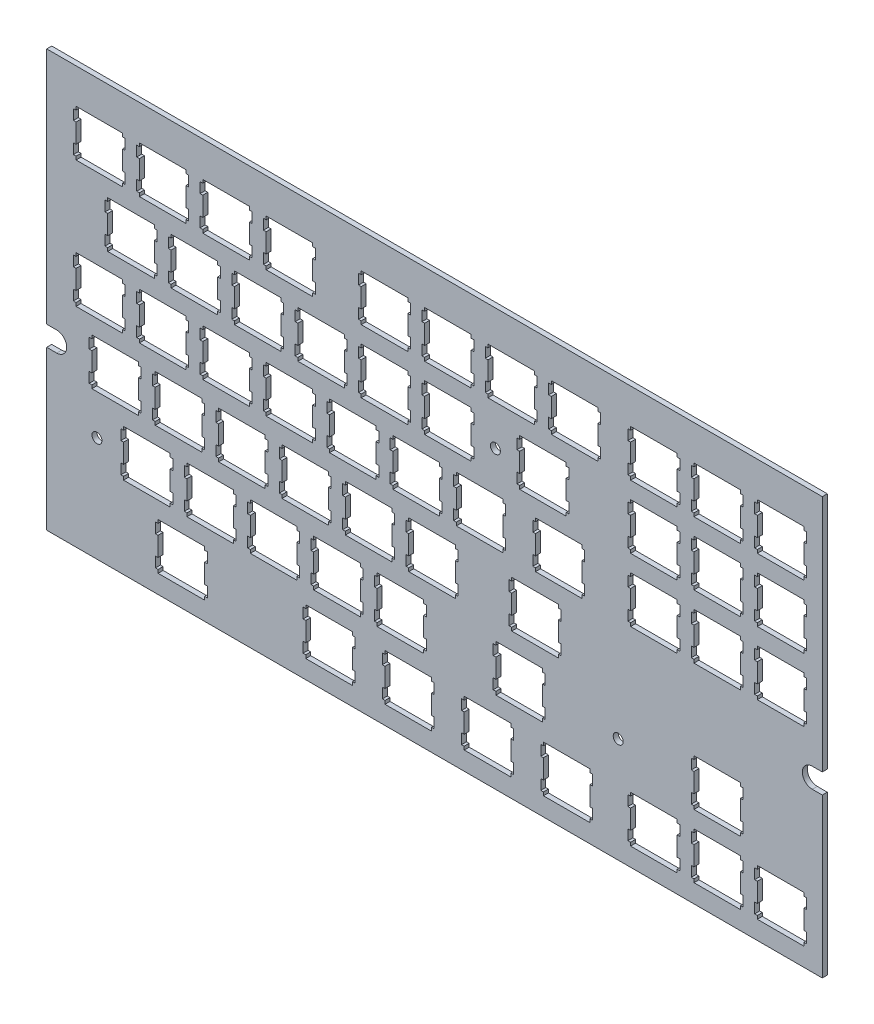
SolidWorks part; units mm, degrees
ref_plane "前视基准面" through (0, 0, 0) normal (0, 0, 1) x (1, 0, 0)
ref_plane "上视基准面" through (0, 0, 0) normal (0, 1, 0) x (1, 0, 0)
ref_plane "右视基准面" through (0, 0, 0) normal (1, 0, 0) x (0, 0, -1)
sketch "Model" plane through (0, 0, 0) normal (0, 0, 1) x (1, 0, 0)
  line L0 (613.9736, 77.7964) -> (613.9736, 76.796)
  line L1 (613.9736, 76.796) -> (613.1726, 76.796)
  line L2 (613.1726, 76.796) -> (613.1726, 73.6967)
  line L3 (613.1726, 73.6967) -> (613.9736, 73.6967)
  line L4 (613.9736, 73.6967) -> (613.9736, 67.8952)
  line L5 (613.9736, 67.8952) -> (613.1726, 67.8952)
  line L6 (613.1726, 67.8952) -> (613.1726, 64.796)
  line L7 (613.1726, 64.796) -> (613.9736, 64.796)
  line L8 (613.9736, 64.796) -> (613.9736, 63.7955)
  line L9 (613.9736, 63.7955) -> (627.9736, 63.7955)
  line L10 (627.9736, 63.7955) -> (627.9736, 64.796)
  line L11 (627.9736, 64.796) -> (628.7726, 64.796)
  line L12 (628.7726, 64.796) -> (628.7726, 67.8952)
  line L13 (628.7726, 67.8952) -> (627.9736, 67.8952)
  line L14 (627.9736, 67.8952) -> (627.9736, 73.6967)
  line L15 (627.9736, 73.6967) -> (628.7726, 73.6967)
  line L16 (628.7726, 73.6967) -> (628.7726, 76.796)
  line L17 (628.7726, 76.796) -> (627.9736, 76.796)
  line L18 (627.9736, 76.796) -> (627.9736, 77.7964)
  line L19 (627.9736, 77.7964) -> (613.9736, 77.7964)
  line L20 (594.9236, 77.7964) -> (594.9236, 76.796)
  line L21 (594.9236, 76.796) -> (594.1226, 76.796)
  line L22 (594.1226, 76.796) -> (594.1226, 73.6967)
  line L23 (594.1226, 73.6967) -> (594.9236, 73.6967)
  line L24 (594.9236, 73.6967) -> (594.9236, 67.8952)
  line L25 (594.9236, 67.8952) -> (594.1226, 67.8952)
  line L26 (594.1226, 67.8952) -> (594.1226, 64.796)
  line L27 (594.1226, 64.796) -> (594.9236, 64.796)
  line L28 (594.9236, 64.796) -> (594.9236, 63.7955)
  line L29 (594.9236, 63.7955) -> (608.9236, 63.7955)
  line L30 (608.9236, 63.7955) -> (608.9236, 64.796)
  line L31 (608.9236, 64.796) -> (609.7226, 64.796)
  line L32 (609.7226, 64.796) -> (609.7226, 67.8952)
  line L33 (609.7226, 67.8952) -> (608.9236, 67.8952)
  line L34 (608.9236, 67.8952) -> (608.9236, 73.6967)
  line L35 (608.9236, 73.6967) -> (609.7226, 73.6967)
  line L36 (609.7226, 73.6967) -> (609.7226, 76.796)
  line L37 (609.7226, 76.796) -> (608.9236, 76.796)
  line L38 (608.9236, 76.796) -> (608.9236, 77.7964)
  line L39 (608.9236, 77.7964) -> (594.9236, 77.7964)
  line L40 (575.8736, 77.7964) -> (575.8736, 76.796)
  line L41 (575.8736, 76.796) -> (575.0726, 76.796)
  line L42 (575.0726, 76.796) -> (575.0726, 73.6967)
  line L43 (575.0726, 73.6967) -> (575.8736, 73.6967)
  line L44 (575.8736, 73.6967) -> (575.8736, 67.8952)
  line L45 (575.8736, 67.8952) -> (575.0726, 67.8952)
  line L46 (575.0726, 67.8952) -> (575.0726, 64.796)
  line L47 (575.0726, 64.796) -> (575.8736, 64.796)
  line L48 (575.8736, 64.796) -> (575.8736, 63.7955)
  line L49 (575.8736, 63.7955) -> (589.8736, 63.7955)
  line L50 (589.8736, 63.7955) -> (589.8736, 64.796)
  line L51 (589.8736, 64.796) -> (590.6726, 64.796)
  line L52 (590.6726, 64.796) -> (590.6726, 67.8952)
  line L53 (590.6726, 67.8952) -> (589.8736, 67.8952)
  line L54 (589.8736, 67.8952) -> (589.8736, 73.6967)
  line L55 (589.8736, 73.6967) -> (590.6726, 73.6967)
  line L56 (590.6726, 73.6967) -> (590.6726, 76.796)
  line L57 (590.6726, 76.796) -> (589.8736, 76.796)
  line L58 (589.8736, 76.796) -> (589.8736, 77.7964)
  line L59 (589.8736, 77.7964) -> (575.8736, 77.7964)
  line L60 (549.6786, 77.7964) -> (549.6786, 76.796)
  line L61 (549.6786, 76.796) -> (548.8796, 76.796)
  line L62 (548.8796, 76.796) -> (548.8796, 73.6967)
  line L63 (548.8796, 73.6967) -> (549.6786, 73.6967)
  line L64 (549.6786, 73.6967) -> (549.6786, 67.8952)
  line L65 (549.6786, 67.8952) -> (548.8796, 67.8952)
  line L66 (548.8796, 67.8952) -> (548.8796, 64.796)
  line L67 (548.8796, 64.796) -> (549.6786, 64.796)
  line L68 (549.6786, 64.796) -> (549.6786, 63.7955)
  line L69 (549.6786, 63.7955) -> (563.6796, 63.7955)
  line L70 (563.6796, 63.7955) -> (563.6796, 64.796)
  line L71 (563.6796, 64.796) -> (564.4786, 64.796)
  line L72 (564.4786, 64.796) -> (564.4786, 67.8952)
  line L73 (564.4786, 67.8952) -> (563.6796, 67.8952)
  line L74 (563.6796, 67.8952) -> (563.6796, 73.6967)
  line L75 (563.6796, 73.6967) -> (564.4786, 73.6967)
  line L76 (564.4786, 73.6967) -> (564.4786, 76.796)
  line L77 (564.4786, 76.796) -> (563.6796, 76.796)
  line L78 (563.6796, 76.796) -> (563.6796, 77.7964)
  line L79 (563.6796, 77.7964) -> (549.6786, 77.7964)
  line L80 (525.8676, 77.7964) -> (525.8676, 76.796)
  line L81 (525.8676, 76.796) -> (525.0666, 76.796)
  line L82 (525.0666, 76.796) -> (525.0666, 73.6967)
  line L83 (525.0666, 73.6967) -> (525.8676, 73.6967)
  line L84 (525.8676, 73.6967) -> (525.8676, 67.8952)
  line L85 (525.8676, 67.8952) -> (525.0666, 67.8952)
  line L86 (525.0666, 67.8952) -> (525.0666, 64.796)
  line L87 (525.0666, 64.796) -> (525.8676, 64.796)
  line L88 (525.8676, 64.796) -> (525.8676, 63.7955)
  line L89 (525.8676, 63.7955) -> (539.8666, 63.7955)
  line L90 (539.8666, 63.7955) -> (539.8666, 64.796)
  line L91 (539.8666, 64.796) -> (540.6676, 64.796)
  line L92 (540.6676, 64.796) -> (540.6676, 67.8952)
  line L93 (540.6676, 67.8952) -> (539.8666, 67.8952)
  line L94 (539.8666, 67.8952) -> (539.8666, 73.6967)
  line L95 (539.8666, 73.6967) -> (540.6676, 73.6967)
  line L96 (540.6676, 73.6967) -> (540.6676, 76.796)
  line L97 (540.6676, 76.796) -> (539.8666, 76.796)
  line L98 (539.8666, 76.796) -> (539.8666, 77.7964)
  line L99 (539.8666, 77.7964) -> (525.8676, 77.7964)
  line L100 (502.0536, 77.7964) -> (502.0536, 76.796)
  line L101 (502.0536, 76.796) -> (501.2546, 76.796)
  line L102 (501.2546, 76.796) -> (501.2546, 73.6967)
  line L103 (501.2546, 73.6967) -> (502.0536, 73.6967)
  line L104 (502.0536, 73.6967) -> (502.0536, 67.8952)
  line L105 (502.0536, 67.8952) -> (501.2546, 67.8952)
  line L106 (501.2546, 67.8952) -> (501.2546, 64.796)
  line L107 (501.2546, 64.796) -> (502.0536, 64.796)
  line L108 (502.0536, 64.796) -> (502.0536, 63.7955)
  line L109 (502.0536, 63.7955) -> (516.0546, 63.7955)
  line L110 (516.0546, 63.7955) -> (516.0546, 64.796)
  line L111 (516.0546, 64.796) -> (516.8536, 64.796)
  line L112 (516.8536, 64.796) -> (516.8536, 67.8952)
  line L113 (516.8536, 67.8952) -> (516.0546, 67.8952)
  line L114 (516.0546, 67.8952) -> (516.0546, 73.6967)
  line L115 (516.0546, 73.6967) -> (516.8536, 73.6967)
  line L116 (516.8536, 73.6967) -> (516.8536, 76.796)
  line L117 (516.8536, 76.796) -> (516.0546, 76.796)
  line L118 (516.0546, 76.796) -> (516.0546, 77.7964)
  line L119 (516.0546, 77.7964) -> (502.0536, 77.7964)
  line L120 (478.2426, 77.7964) -> (478.2426, 76.796)
  line L121 (478.2426, 76.796) -> (477.4416, 76.796)
  line L122 (477.4416, 76.796) -> (477.4416, 73.6967)
  line L123 (477.4416, 73.6967) -> (478.2426, 73.6967)
  line L124 (478.2426, 73.6967) -> (478.2426, 67.8952)
  line L125 (478.2426, 67.8952) -> (477.4416, 67.8952)
  line L126 (477.4416, 67.8952) -> (477.4416, 64.796)
  line L127 (477.4416, 64.796) -> (478.2426, 64.796)
  line L128 (478.2426, 64.796) -> (478.2426, 63.7955)
  line L129 (478.2426, 63.7955) -> (492.2416, 63.7955)
  line L130 (492.2416, 63.7955) -> (492.2416, 64.796)
  line L131 (492.2416, 64.796) -> (493.0426, 64.796)
  line L132 (493.0426, 64.796) -> (493.0426, 67.8952)
  line L133 (493.0426, 67.8952) -> (492.2416, 67.8952)
  line L134 (492.2416, 67.8952) -> (492.2416, 73.6967)
  line L135 (492.2416, 73.6967) -> (493.0426, 73.6967)
  line L136 (493.0426, 73.6967) -> (493.0426, 76.796)
  line L137 (493.0426, 76.796) -> (492.2416, 76.796)
  line L138 (492.2416, 76.796) -> (492.2416, 77.7964)
  line L139 (492.2416, 77.7964) -> (478.2426, 77.7964)
  line L140 (594.9236, 96.8449) -> (594.9236, 95.8446)
  line L141 (594.9236, 95.8446) -> (594.1226, 95.8446)
  line L142 (594.1226, 95.8446) -> (594.1226, 92.7467)
  line L143 (594.1226, 92.7467) -> (594.9236, 92.7467)
  line L144 (594.9236, 92.7467) -> (594.9236, 86.9452)
  line L145 (594.9236, 86.9452) -> (594.1226, 86.9452)
  line L146 (594.1226, 86.9452) -> (594.1226, 83.8446)
  line L147 (594.1226, 83.8446) -> (594.9236, 83.8446)
  line L148 (594.9236, 83.8446) -> (594.9236, 82.8455)
  line L149 (594.9236, 82.8455) -> (608.9236, 82.8455)
  line L150 (608.9236, 82.8455) -> (608.9236, 83.8446)
  line L151 (608.9236, 83.8446) -> (609.7226, 83.8446)
  line L152 (609.7226, 83.8446) -> (609.7226, 86.9452)
  line L153 (609.7226, 86.9452) -> (608.9236, 86.9452)
  line L154 (608.9236, 86.9452) -> (608.9236, 92.7467)
  line L155 (608.9236, 92.7467) -> (609.7226, 92.7467)
  line L156 (609.7226, 92.7467) -> (609.7226, 95.8446)
  line L157 (609.7226, 95.8446) -> (608.9236, 95.8446)
  line L158 (608.9236, 95.8446) -> (608.9236, 96.8449)
  line L159 (608.9236, 96.8449) -> (594.9236, 96.8449)
  line L160 (499.6736, 96.8449) -> (499.6736, 95.8446)
  line L161 (499.6736, 95.8446) -> (498.8726, 95.8446)
  line L162 (498.8726, 95.8446) -> (498.8726, 92.7467)
  line L163 (498.8726, 92.7467) -> (499.6736, 92.7467)
  line L164 (499.6736, 92.7467) -> (499.6736, 86.9452)
  line L165 (499.6736, 86.9452) -> (498.8726, 86.9452)
  line L166 (498.8726, 86.9452) -> (498.8726, 83.8446)
  line L167 (498.8726, 83.8446) -> (499.6736, 83.8446)
  line L168 (499.6736, 83.8446) -> (499.6736, 82.8455)
  line L169 (499.6736, 82.8455) -> (513.6736, 82.8455)
  line L170 (513.6736, 82.8455) -> (513.6736, 83.8446)
  line L171 (513.6736, 83.8446) -> (514.4726, 83.8446)
  line L172 (514.4726, 83.8446) -> (514.4726, 86.9452)
  line L173 (514.4726, 86.9452) -> (513.6736, 86.9452)
  line L174 (513.6736, 86.9452) -> (513.6736, 92.7467)
  line L175 (513.6736, 92.7467) -> (514.4726, 92.7467)
  line L176 (514.4726, 92.7467) -> (514.4726, 95.8446)
  line L177 (514.4726, 95.8446) -> (513.6736, 95.8446)
  line L178 (513.6736, 95.8446) -> (513.6736, 96.8449)
  line L179 (513.6736, 96.8449) -> (499.6736, 96.8449)
  line L180 (480.6236, 96.8449) -> (480.6236, 95.8446)
  line L181 (480.6236, 95.8446) -> (479.8226, 95.8446)
  line L182 (479.8226, 95.8446) -> (479.8226, 92.7467)
  line L183 (479.8226, 92.7467) -> (480.6236, 92.7467)
  line L184 (480.6236, 92.7467) -> (480.6236, 86.9452)
  line L185 (480.6236, 86.9452) -> (479.8226, 86.9452)
  line L186 (479.8226, 86.9452) -> (479.8226, 83.8446)
  line L187 (479.8226, 83.8446) -> (480.6236, 83.8446)
  line L188 (480.6236, 83.8446) -> (480.6236, 82.8455)
  line L189 (480.6236, 82.8455) -> (494.6236, 82.8455)
  line L190 (494.6236, 82.8455) -> (494.6236, 83.8446)
  line L191 (494.6236, 83.8446) -> (495.4226, 83.8446)
  line L192 (495.4226, 83.8446) -> (495.4226, 86.9452)
  line L193 (495.4226, 86.9452) -> (494.6236, 86.9452)
  line L194 (494.6236, 86.9452) -> (494.6236, 92.7467)
  line L195 (494.6236, 92.7467) -> (495.4226, 92.7467)
  line L196 (495.4226, 92.7467) -> (495.4226, 95.8446)
  line L197 (495.4226, 95.8446) -> (494.6236, 95.8446)
  line L198 (494.6236, 95.8446) -> (494.6236, 96.8449)
  line L199 (494.6236, 96.8449) -> (480.6236, 96.8449)
  line L200 (461.5736, 96.8449) -> (461.5736, 95.8446)
  line L201 (461.5736, 95.8446) -> (460.7726, 95.8446)
  line L202 (460.7726, 95.8446) -> (460.7726, 92.7467)
  line L203 (460.7726, 92.7467) -> (461.5736, 92.7467)
  line L204 (461.5736, 92.7467) -> (461.5736, 86.9452)
  line L205 (461.5736, 86.9452) -> (460.7726, 86.9452)
  line L206 (460.7726, 86.9452) -> (460.7726, 83.8446)
  line L207 (460.7726, 83.8446) -> (461.5736, 83.8446)
  line L208 (461.5736, 83.8446) -> (461.5736, 82.8455)
  line L209 (461.5736, 82.8455) -> (475.5736, 82.8455)
  line L210 (475.5736, 82.8455) -> (475.5736, 83.8446)
  line L211 (475.5736, 83.8446) -> (476.3726, 83.8446)
  line L212 (476.3726, 83.8446) -> (476.3726, 86.9452)
  line L213 (476.3726, 86.9452) -> (475.5736, 86.9452)
  line L214 (475.5736, 86.9452) -> (475.5736, 92.7467)
  line L215 (475.5736, 92.7467) -> (476.3726, 92.7467)
  line L216 (476.3726, 92.7467) -> (476.3726, 95.8446)
  line L217 (476.3726, 95.8446) -> (475.5736, 95.8446)
  line L218 (475.5736, 95.8446) -> (475.5736, 96.8449)
  line L219 (475.5736, 96.8449) -> (461.5736, 96.8449)
  line L220 (442.5236, 96.8449) -> (442.5236, 95.8446)
  line L221 (442.5236, 95.8446) -> (441.7226, 95.8446)
  line L222 (441.7226, 95.8446) -> (441.7226, 92.7467)
  line L223 (441.7226, 92.7467) -> (442.5236, 92.7467)
  line L224 (442.5236, 92.7467) -> (442.5236, 86.9452)
  line L225 (442.5236, 86.9452) -> (441.7226, 86.9452)
  line L226 (441.7226, 86.9452) -> (441.7226, 83.8446)
  line L227 (441.7226, 83.8446) -> (442.5236, 83.8446)
  line L228 (442.5236, 83.8446) -> (442.5236, 82.8455)
  line L229 (442.5236, 82.8455) -> (456.5236, 82.8455)
  line L230 (456.5236, 82.8455) -> (456.5236, 83.8446)
  line L231 (456.5236, 83.8446) -> (457.3226, 83.8446)
  line L232 (457.3226, 83.8446) -> (457.3226, 86.9452)
  line L233 (457.3226, 86.9452) -> (456.5236, 86.9452)
  line L234 (456.5236, 86.9452) -> (456.5236, 92.7467)
  line L235 (456.5236, 92.7467) -> (457.3226, 92.7467)
  line L236 (457.3226, 92.7467) -> (457.3226, 95.8446)
  line L237 (457.3226, 95.8446) -> (456.5236, 95.8446)
  line L238 (456.5236, 95.8446) -> (456.5236, 96.8449)
  line L239 (456.5236, 96.8449) -> (442.5236, 96.8449)
  line L240 (423.4736, 96.8449) -> (423.4736, 95.8446)
  line L241 (423.4736, 95.8446) -> (422.6726, 95.8446)
  line L242 (422.6726, 95.8446) -> (422.6726, 92.7467)
  line L243 (422.6726, 92.7467) -> (423.4736, 92.7467)
  line L244 (423.4736, 92.7467) -> (423.4736, 86.9452)
  line L245 (423.4736, 86.9452) -> (422.6726, 86.9452)
  line L246 (422.6726, 86.9452) -> (422.6726, 83.8446)
  line L247 (422.6726, 83.8446) -> (423.4736, 83.8446)
  line L248 (423.4736, 83.8446) -> (423.4736, 82.8455)
  line L249 (423.4736, 82.8455) -> (437.4736, 82.8455)
  line L250 (437.4736, 82.8455) -> (437.4736, 83.8446)
  line L251 (437.4736, 83.8446) -> (438.2726, 83.8446)
  line L252 (438.2726, 83.8446) -> (438.2726, 86.9452)
  line L253 (438.2726, 86.9452) -> (437.4736, 86.9452)
  line L254 (437.4736, 86.9452) -> (437.4736, 92.7467)
  line L255 (437.4736, 92.7467) -> (438.2726, 92.7467)
  line L256 (438.2726, 92.7467) -> (438.2726, 95.8446)
  line L257 (438.2726, 95.8446) -> (437.4736, 95.8446)
  line L258 (437.4736, 95.8446) -> (437.4736, 96.8449)
  line L259 (437.4736, 96.8449) -> (423.4736, 96.8449)
  line L260 (540.1536, 115.895) -> (540.1536, 114.8945)
  line L261 (540.1536, 114.8945) -> (539.3526, 114.8945)
  line L262 (539.3526, 114.8945) -> (539.3526, 111.7967)
  line L263 (539.3526, 111.7967) -> (540.1536, 111.7967)
  line L264 (540.1536, 111.7967) -> (540.1536, 105.9953)
  line L265 (540.1536, 105.9953) -> (539.3526, 105.9953)
  line L266 (539.3526, 105.9953) -> (539.3526, 102.8947)
  line L267 (539.3526, 102.8947) -> (540.1536, 102.8947)
  line L268 (540.1536, 102.8947) -> (540.1536, 101.8957)
  line L269 (540.1536, 101.8957) -> (554.1546, 101.8957)
  line L270 (554.1546, 101.8957) -> (554.1546, 102.8947)
  line L271 (554.1546, 102.8947) -> (554.9536, 102.8947)
  line L272 (554.9536, 102.8947) -> (554.9536, 105.9953)
  line L273 (554.9536, 105.9953) -> (554.1546, 105.9953)
  line L274 (554.1546, 105.9953) -> (554.1546, 111.7967)
  line L275 (554.1546, 111.7967) -> (554.9536, 111.7967)
  line L276 (554.9536, 111.7967) -> (554.9536, 114.8945)
  line L277 (554.9536, 114.8945) -> (554.1546, 114.8945)
  line L278 (554.1546, 114.8945) -> (554.1546, 115.895)
  line L279 (554.1546, 115.895) -> (540.1536, 115.895)
  line L280 (509.1986, 115.895) -> (509.1986, 114.8945)
  line L281 (509.1986, 114.8945) -> (508.3976, 114.8945)
  line L282 (508.3976, 114.8945) -> (508.3976, 111.7967)
  line L283 (508.3976, 111.7967) -> (509.1986, 111.7967)
  line L284 (509.1986, 111.7967) -> (509.1986, 105.9953)
  line L285 (509.1986, 105.9953) -> (508.3976, 105.9953)
  line L286 (508.3976, 105.9953) -> (508.3976, 102.8947)
  line L287 (508.3976, 102.8947) -> (509.1986, 102.8947)
  line L288 (509.1986, 102.8947) -> (509.1986, 101.8957)
  line L289 (509.1986, 101.8957) -> (523.1986, 101.8957)
  line L290 (523.1986, 101.8957) -> (523.1986, 102.8947)
  line L291 (523.1986, 102.8947) -> (523.9976, 102.8947)
  line L292 (523.9976, 102.8947) -> (523.9976, 105.9953)
  line L293 (523.9976, 105.9953) -> (523.1986, 105.9953)
  line L294 (523.1986, 105.9953) -> (523.1986, 111.7967)
  line L295 (523.1986, 111.7967) -> (523.9976, 111.7967)
  line L296 (523.9976, 111.7967) -> (523.9976, 114.8945)
  line L297 (523.9976, 114.8945) -> (523.1986, 114.8945)
  line L298 (523.1986, 114.8945) -> (523.1986, 115.895)
  line L299 (523.1986, 115.895) -> (509.1986, 115.895)
  line L300 (490.1486, 115.895) -> (490.1486, 114.8945)
  line L301 (490.1486, 114.8945) -> (489.3476, 114.8945)
  line L302 (489.3476, 114.8945) -> (489.3476, 111.7967)
  line L303 (489.3476, 111.7967) -> (490.1486, 111.7967)
  line L304 (490.1486, 111.7967) -> (490.1486, 105.9953)
  line L305 (490.1486, 105.9953) -> (489.3476, 105.9953)
  line L306 (489.3476, 105.9953) -> (489.3476, 102.8947)
  line L307 (489.3476, 102.8947) -> (490.1486, 102.8947)
  line L308 (490.1486, 102.8947) -> (490.1486, 101.8957)
  line L309 (490.1486, 101.8957) -> (504.1486, 101.8957)
  line L310 (504.1486, 101.8957) -> (504.1486, 102.8947)
  line L311 (504.1486, 102.8947) -> (504.9476, 102.8947)
  line L312 (504.9476, 102.8947) -> (504.9476, 105.9953)
  line L313 (504.9476, 105.9953) -> (504.1486, 105.9953)
  line L314 (504.1486, 105.9953) -> (504.1486, 111.7967)
  line L315 (504.1486, 111.7967) -> (504.9476, 111.7967)
  line L316 (504.9476, 111.7967) -> (504.9476, 114.8945)
  line L317 (504.9476, 114.8945) -> (504.1486, 114.8945)
  line L318 (504.1486, 114.8945) -> (504.1486, 115.895)
  line L319 (504.1486, 115.895) -> (490.1486, 115.895)
  line L320 (471.0986, 115.895) -> (471.0986, 114.8945)
  line L321 (471.0986, 114.8945) -> (470.2976, 114.8945)
  line L322 (470.2976, 114.8945) -> (470.2976, 111.7967)
  line L323 (470.2976, 111.7967) -> (471.0986, 111.7967)
  line L324 (471.0986, 111.7967) -> (471.0986, 105.9953)
  line L325 (471.0986, 105.9953) -> (470.2976, 105.9953)
  line L326 (470.2976, 105.9953) -> (470.2976, 102.8947)
  line L327 (470.2976, 102.8947) -> (471.0986, 102.8947)
  line L328 (471.0986, 102.8947) -> (471.0986, 101.8957)
  line L329 (471.0986, 101.8957) -> (485.0986, 101.8957)
  line L330 (485.0986, 101.8957) -> (485.0986, 102.8947)
  line L331 (485.0986, 102.8947) -> (485.8976, 102.8947)
  line L332 (485.8976, 102.8947) -> (485.8976, 105.9953)
  line L333 (485.8976, 105.9953) -> (485.0986, 105.9953)
  line L334 (485.0986, 105.9953) -> (485.0986, 111.7967)
  line L335 (485.0986, 111.7967) -> (485.8976, 111.7967)
  line L336 (485.8976, 111.7967) -> (485.8976, 114.8945)
  line L337 (485.8976, 114.8945) -> (485.0986, 114.8945)
  line L338 (485.0986, 114.8945) -> (485.0986, 115.895)
  line L339 (485.0986, 115.895) -> (471.0986, 115.895)
  line L340 (452.0486, 115.895) -> (452.0486, 114.8945)
  line L341 (452.0486, 114.8945) -> (451.2476, 114.8945)
  line L342 (451.2476, 114.8945) -> (451.2476, 111.7967)
  line L343 (451.2476, 111.7967) -> (452.0486, 111.7967)
  line L344 (452.0486, 111.7967) -> (452.0486, 105.9953)
  line L345 (452.0486, 105.9953) -> (451.2476, 105.9953)
  line L346 (451.2476, 105.9953) -> (451.2476, 102.8947)
  line L347 (451.2476, 102.8947) -> (452.0486, 102.8947)
  line L348 (452.0486, 102.8947) -> (452.0486, 101.8957)
  line L349 (452.0486, 101.8957) -> (466.0486, 101.8957)
  line L350 (466.0486, 101.8957) -> (466.0486, 102.8947)
  line L351 (466.0486, 102.8947) -> (466.8476, 102.8947)
  line L352 (466.8476, 102.8947) -> (466.8476, 105.9953)
  line L353 (466.8476, 105.9953) -> (466.0486, 105.9953)
  line L354 (466.0486, 105.9953) -> (466.0486, 111.7967)
  line L355 (466.0486, 111.7967) -> (466.8476, 111.7967)
  line L356 (466.8476, 111.7967) -> (466.8476, 114.8945)
  line L357 (466.8476, 114.8945) -> (466.0486, 114.8945)
  line L358 (466.0486, 114.8945) -> (466.0486, 115.895)
  line L359 (466.0486, 115.895) -> (452.0486, 115.895)
  line L360 (432.9986, 115.895) -> (432.9986, 114.8945)
  line L361 (432.9986, 114.8945) -> (432.1976, 114.8945)
  line L362 (432.1976, 114.8945) -> (432.1976, 111.7967)
  line L363 (432.1976, 111.7967) -> (432.9986, 111.7967)
  line L364 (432.9986, 111.7967) -> (432.9986, 105.9953)
  line L365 (432.9986, 105.9953) -> (432.1976, 105.9953)
  line L366 (432.1976, 105.9953) -> (432.1976, 102.8947)
  line L367 (432.1976, 102.8947) -> (432.9986, 102.8947)
  line L368 (432.9986, 102.8947) -> (432.9986, 101.8957)
  line L369 (432.9986, 101.8957) -> (446.9986, 101.8957)
  line L370 (446.9986, 101.8957) -> (446.9986, 102.8947)
  line L371 (446.9986, 102.8947) -> (447.7976, 102.8947)
  line L372 (447.7976, 102.8947) -> (447.7976, 105.9953)
  line L373 (447.7976, 105.9953) -> (446.9986, 105.9953)
  line L374 (446.9986, 105.9953) -> (446.9986, 111.7967)
  line L375 (446.9986, 111.7967) -> (447.7976, 111.7967)
  line L376 (447.7976, 111.7967) -> (447.7976, 114.8945)
  line L377 (447.7976, 114.8945) -> (446.9986, 114.8945)
  line L378 (446.9986, 114.8945) -> (446.9986, 115.895)
  line L379 (446.9986, 115.895) -> (432.9986, 115.895)
  line L380 (413.9486, 115.895) -> (413.9486, 114.8945)
  line L381 (413.9486, 114.8945) -> (413.1476, 114.8945)
  line L382 (413.1476, 114.8945) -> (413.1476, 111.7967)
  line L383 (413.1476, 111.7967) -> (413.9486, 111.7967)
  line L384 (413.9486, 111.7967) -> (413.9486, 105.9953)
  line L385 (413.9486, 105.9953) -> (413.1476, 105.9953)
  line L386 (413.1476, 105.9953) -> (413.1476, 102.8947)
  line L387 (413.1476, 102.8947) -> (413.9486, 102.8947)
  line L388 (413.9486, 102.8947) -> (413.9486, 101.8957)
  line L389 (413.9486, 101.8957) -> (427.9486, 101.8957)
  line L390 (427.9486, 101.8957) -> (427.9486, 102.8947)
  line L391 (427.9486, 102.8947) -> (428.7476, 102.8947)
  line L392 (428.7476, 102.8947) -> (428.7476, 105.9953)
  line L393 (428.7476, 105.9953) -> (427.9486, 105.9953)
  line L394 (427.9486, 105.9953) -> (427.9486, 111.7967)
  line L395 (427.9486, 111.7967) -> (428.7476, 111.7967)
  line L396 (428.7476, 111.7967) -> (428.7476, 114.8945)
  line L397 (428.7476, 114.8945) -> (427.9486, 114.8945)
  line L398 (427.9486, 114.8945) -> (427.9486, 115.895)
  line L399 (427.9486, 115.895) -> (413.9486, 115.895)
  line L400 (613.9736, 134.945) -> (613.9736, 133.9445)
  line L401 (613.9736, 133.9445) -> (613.1726, 133.9445)
  line L402 (613.1726, 133.9445) -> (613.1726, 130.8453)
  line L403 (613.1726, 130.8453) -> (613.9736, 130.8453)
  line L404 (613.9736, 130.8453) -> (613.9736, 125.0453)
  line L405 (613.9736, 125.0453) -> (613.1726, 125.0453)
  line L406 (613.1726, 125.0453) -> (613.1726, 121.9447)
  line L407 (613.1726, 121.9447) -> (613.9736, 121.9447)
  line L408 (613.9736, 121.9447) -> (613.9736, 120.9457)
  line L409 (613.9736, 120.9457) -> (627.9736, 120.9457)
  line L410 (627.9736, 120.9457) -> (627.9736, 121.9447)
  line L411 (627.9736, 121.9447) -> (628.7726, 121.9447)
  line L412 (628.7726, 121.9447) -> (628.7726, 125.0453)
  line L413 (628.7726, 125.0453) -> (627.9736, 125.0453)
  line L414 (627.9736, 125.0453) -> (627.9736, 130.8453)
  line L415 (627.9736, 130.8453) -> (628.7726, 130.8453)
  line L416 (628.7726, 130.8453) -> (628.7726, 133.9445)
  line L417 (628.7726, 133.9445) -> (627.9736, 133.9445)
  line L418 (627.9736, 133.9445) -> (627.9736, 134.945)
  line L419 (627.9736, 134.945) -> (613.9736, 134.945)
  line L420 (594.9236, 134.945) -> (594.9236, 133.9445)
  line L421 (594.9236, 133.9445) -> (594.1226, 133.9445)
  line L422 (594.1226, 133.9445) -> (594.1226, 130.8453)
  line L423 (594.1226, 130.8453) -> (594.9236, 130.8453)
  line L424 (594.9236, 130.8453) -> (594.9236, 125.0453)
  line L425 (594.9236, 125.0453) -> (594.1226, 125.0453)
  line L426 (594.1226, 125.0453) -> (594.1226, 121.9447)
  line L427 (594.1226, 121.9447) -> (594.9236, 121.9447)
  line L428 (594.9236, 121.9447) -> (594.9236, 120.9457)
  line L429 (594.9236, 120.9457) -> (608.9236, 120.9457)
  line L430 (608.9236, 120.9457) -> (608.9236, 121.9447)
  line L431 (608.9236, 121.9447) -> (609.7226, 121.9447)
  line L432 (609.7226, 121.9447) -> (609.7226, 125.0453)
  line L433 (609.7226, 125.0453) -> (608.9236, 125.0453)
  line L434 (608.9236, 125.0453) -> (608.9236, 130.8453)
  line L435 (608.9236, 130.8453) -> (609.7226, 130.8453)
  line L436 (609.7226, 130.8453) -> (609.7226, 133.9445)
  line L437 (609.7226, 133.9445) -> (608.9236, 133.9445)
  line L438 (608.9236, 133.9445) -> (608.9236, 134.945)
  line L439 (608.9236, 134.945) -> (594.9236, 134.945)
  line L440 (575.8736, 134.945) -> (575.8736, 133.9445)
  line L441 (575.8736, 133.9445) -> (575.0726, 133.9445)
  line L442 (575.0726, 133.9445) -> (575.0726, 130.8453)
  line L443 (575.0726, 130.8453) -> (575.8736, 130.8453)
  line L444 (575.8736, 130.8453) -> (575.8736, 125.0453)
  line L445 (575.8736, 125.0453) -> (575.0726, 125.0453)
  line L446 (575.0726, 125.0453) -> (575.0726, 121.9447)
  line L447 (575.0726, 121.9447) -> (575.8736, 121.9447)
  line L448 (575.8736, 121.9447) -> (575.8736, 120.9457)
  line L449 (575.8736, 120.9457) -> (589.8736, 120.9457)
  line L450 (589.8736, 120.9457) -> (589.8736, 121.9447)
  line L451 (589.8736, 121.9447) -> (590.6726, 121.9447)
  line L452 (590.6726, 121.9447) -> (590.6726, 125.0453)
  line L453 (590.6726, 125.0453) -> (589.8736, 125.0453)
  line L454 (589.8736, 125.0453) -> (589.8736, 130.8453)
  line L455 (589.8736, 130.8453) -> (590.6726, 130.8453)
  line L456 (590.6726, 130.8453) -> (590.6726, 133.9445)
  line L457 (590.6726, 133.9445) -> (589.8736, 133.9445)
  line L458 (589.8736, 133.9445) -> (589.8736, 134.945)
  line L459 (589.8736, 134.945) -> (575.8736, 134.945)
  line L460 (547.2986, 134.945) -> (547.2986, 133.9445)
  line L461 (547.2986, 133.9445) -> (546.4976, 133.9445)
  line L462 (546.4976, 133.9445) -> (546.4976, 130.8453)
  line L463 (546.4976, 130.8453) -> (547.2986, 130.8453)
  line L464 (547.2986, 130.8453) -> (547.2986, 125.0453)
  line L465 (547.2986, 125.0453) -> (546.4976, 125.0453)
  line L466 (546.4976, 125.0453) -> (546.4976, 121.9447)
  line L467 (546.4976, 121.9447) -> (547.2986, 121.9447)
  line L468 (547.2986, 121.9447) -> (547.2986, 120.9457)
  line L469 (547.2986, 120.9457) -> (561.2986, 120.9457)
  line L470 (561.2986, 120.9457) -> (561.2986, 121.9447)
  line L471 (561.2986, 121.9447) -> (562.0976, 121.9447)
  line L472 (562.0976, 121.9447) -> (562.0976, 125.0453)
  line L473 (562.0976, 125.0453) -> (561.2986, 125.0453)
  line L474 (561.2986, 125.0453) -> (561.2986, 130.8453)
  line L475 (561.2986, 130.8453) -> (562.0976, 130.8453)
  line L476 (562.0976, 130.8453) -> (562.0976, 133.9445)
  line L477 (562.0976, 133.9445) -> (561.2986, 133.9445)
  line L478 (561.2986, 133.9445) -> (561.2986, 134.945)
  line L479 (561.2986, 134.945) -> (547.2986, 134.945)
  line L480 (523.4866, 134.945) -> (523.4866, 133.9445)
  line L481 (523.4866, 133.9445) -> (522.6856, 133.9445)
  line L482 (522.6856, 133.9445) -> (522.6856, 130.8453)
  line L483 (522.6856, 130.8453) -> (523.4866, 130.8453)
  line L484 (523.4866, 130.8453) -> (523.4866, 125.0453)
  line L485 (523.4866, 125.0453) -> (522.6856, 125.0453)
  line L486 (522.6856, 125.0453) -> (522.6856, 121.9447)
  line L487 (522.6856, 121.9447) -> (523.4866, 121.9447)
  line L488 (523.4866, 121.9447) -> (523.4866, 120.9457)
  line L489 (523.4866, 120.9457) -> (537.4856, 120.9457)
  line L490 (537.4856, 120.9457) -> (537.4856, 121.9447)
  line L491 (537.4856, 121.9447) -> (538.2866, 121.9447)
  line L492 (538.2866, 121.9447) -> (538.2866, 125.0453)
  line L493 (538.2866, 125.0453) -> (537.4856, 125.0453)
  line L494 (537.4856, 125.0453) -> (537.4856, 130.8453)
  line L495 (537.4856, 130.8453) -> (538.2866, 130.8453)
  line L496 (538.2866, 130.8453) -> (538.2866, 133.9445)
  line L497 (538.2866, 133.9445) -> (537.4856, 133.9445)
  line L498 (537.4856, 133.9445) -> (537.4856, 134.945)
  line L499 (537.4856, 134.945) -> (523.4866, 134.945)
  line L500 (504.4366, 134.945) -> (504.4366, 133.9445)
  line L501 (504.4366, 133.9445) -> (503.6356, 133.9445)
  line L502 (503.6356, 133.9445) -> (503.6356, 130.8453)
  line L503 (503.6356, 130.8453) -> (504.4366, 130.8453)
  line L504 (504.4366, 130.8453) -> (504.4366, 125.0453)
  line L505 (504.4366, 125.0453) -> (503.6356, 125.0453)
  line L506 (503.6356, 125.0453) -> (503.6356, 121.9447)
  line L507 (503.6356, 121.9447) -> (504.4366, 121.9447)
  line L508 (504.4366, 121.9447) -> (504.4366, 120.9457)
  line L509 (504.4366, 120.9457) -> (518.4356, 120.9457)
  line L510 (518.4356, 120.9457) -> (518.4356, 121.9447)
  line L511 (518.4356, 121.9447) -> (519.2366, 121.9447)
  line L512 (519.2366, 121.9447) -> (519.2366, 125.0453)
  line L513 (519.2366, 125.0453) -> (518.4356, 125.0453)
  line L514 (518.4356, 125.0453) -> (518.4356, 130.8453)
  line L515 (518.4356, 130.8453) -> (519.2366, 130.8453)
  line L516 (519.2366, 130.8453) -> (519.2366, 133.9445)
  line L517 (519.2366, 133.9445) -> (518.4356, 133.9445)
  line L518 (518.4356, 133.9445) -> (518.4356, 134.945)
  line L519 (518.4356, 134.945) -> (504.4366, 134.945)
  line L520 (485.3866, 134.945) -> (485.3866, 133.9445)
  line L521 (485.3866, 133.9445) -> (484.5856, 133.9445)
  line L522 (484.5856, 133.9445) -> (484.5856, 130.8453)
  line L523 (484.5856, 130.8453) -> (485.3866, 130.8453)
  line L524 (485.3866, 130.8453) -> (485.3866, 125.0453)
  line L525 (485.3866, 125.0453) -> (484.5856, 125.0453)
  line L526 (484.5856, 125.0453) -> (484.5856, 121.9447)
  line L527 (484.5856, 121.9447) -> (485.3866, 121.9447)
  line L528 (485.3866, 121.9447) -> (485.3866, 120.9457)
  line L529 (485.3866, 120.9457) -> (499.3856, 120.9457)
  line L530 (499.3856, 120.9457) -> (499.3856, 121.9447)
  line L531 (499.3856, 121.9447) -> (500.1866, 121.9447)
  line L532 (500.1866, 121.9447) -> (500.1866, 125.0453)
  line L533 (500.1866, 125.0453) -> (499.3856, 125.0453)
  line L534 (499.3856, 125.0453) -> (499.3856, 130.8453)
  line L535 (499.3856, 130.8453) -> (500.1866, 130.8453)
  line L536 (500.1866, 130.8453) -> (500.1866, 133.9445)
  line L537 (500.1866, 133.9445) -> (499.3856, 133.9445)
  line L538 (499.3856, 133.9445) -> (499.3856, 134.945)
  line L539 (499.3856, 134.945) -> (485.3866, 134.945)
  line L540 (466.3366, 134.945) -> (466.3366, 133.9445)
  line L541 (466.3366, 133.9445) -> (465.5356, 133.9445)
  line L542 (465.5356, 133.9445) -> (465.5356, 130.8453)
  line L543 (465.5356, 130.8453) -> (466.3366, 130.8453)
  line L544 (466.3366, 130.8453) -> (466.3366, 125.0453)
  line L545 (466.3366, 125.0453) -> (465.5356, 125.0453)
  line L546 (465.5356, 125.0453) -> (465.5356, 121.9447)
  line L547 (465.5356, 121.9447) -> (466.3366, 121.9447)
  line L548 (466.3366, 121.9447) -> (466.3366, 120.9457)
  line L549 (466.3366, 120.9457) -> (480.3356, 120.9457)
  line L550 (480.3356, 120.9457) -> (480.3356, 121.9447)
  line L551 (480.3356, 121.9447) -> (481.1366, 121.9447)
  line L552 (481.1366, 121.9447) -> (481.1366, 125.0453)
  line L553 (481.1366, 125.0453) -> (480.3356, 125.0453)
  line L554 (480.3356, 125.0453) -> (480.3356, 130.8453)
  line L555 (480.3356, 130.8453) -> (481.1366, 130.8453)
  line L556 (481.1366, 130.8453) -> (481.1366, 133.9445)
  line L557 (481.1366, 133.9445) -> (480.3356, 133.9445)
  line L558 (480.3356, 133.9445) -> (480.3356, 134.945)
  line L559 (480.3356, 134.945) -> (466.3366, 134.945)
  line L560 (447.2866, 134.945) -> (447.2866, 133.9445)
  line L561 (447.2866, 133.9445) -> (446.4856, 133.9445)
  line L562 (446.4856, 133.9445) -> (446.4856, 130.8453)
  line L563 (446.4856, 130.8453) -> (447.2866, 130.8453)
  line L564 (447.2866, 130.8453) -> (447.2866, 125.0453)
  line L565 (447.2866, 125.0453) -> (446.4856, 125.0453)
  line L566 (446.4856, 125.0453) -> (446.4856, 121.9447)
  line L567 (446.4856, 121.9447) -> (447.2866, 121.9447)
  line L568 (447.2866, 121.9447) -> (447.2866, 120.9457)
  line L569 (447.2866, 120.9457) -> (461.2856, 120.9457)
  line L570 (461.2856, 120.9457) -> (461.2856, 121.9447)
  line L571 (461.2856, 121.9447) -> (462.0866, 121.9447)
  line L572 (462.0866, 121.9447) -> (462.0866, 125.0453)
  line L573 (462.0866, 125.0453) -> (461.2856, 125.0453)
  line L574 (461.2856, 125.0453) -> (461.2856, 130.8453)
  line L575 (461.2856, 130.8453) -> (462.0866, 130.8453)
  line L576 (462.0866, 130.8453) -> (462.0866, 133.9445)
  line L577 (462.0866, 133.9445) -> (461.2856, 133.9445)
  line L578 (461.2856, 133.9445) -> (461.2856, 134.945)
  line L579 (461.2856, 134.945) -> (447.2866, 134.945)
  line L580 (428.2366, 134.945) -> (428.2366, 133.9445)
  line L581 (428.2366, 133.9445) -> (427.4356, 133.9445)
  line L582 (427.4356, 133.9445) -> (427.4356, 130.8453)
  line L583 (427.4356, 130.8453) -> (428.2366, 130.8453)
  line L584 (428.2366, 130.8453) -> (428.2366, 125.0453)
  line L585 (428.2366, 125.0453) -> (427.4356, 125.0453)
  line L586 (427.4356, 125.0453) -> (427.4356, 121.9447)
  line L587 (427.4356, 121.9447) -> (428.2366, 121.9447)
  line L588 (428.2366, 121.9447) -> (428.2366, 120.9457)
  line L589 (428.2366, 120.9457) -> (442.2356, 120.9457)
  line L590 (442.2356, 120.9457) -> (442.2356, 121.9447)
  line L591 (442.2356, 121.9447) -> (443.0366, 121.9447)
  line L592 (443.0366, 121.9447) -> (443.0366, 125.0453)
  line L593 (443.0366, 125.0453) -> (442.2356, 125.0453)
  line L594 (442.2356, 125.0453) -> (442.2356, 130.8453)
  line L595 (442.2356, 130.8453) -> (443.0366, 130.8453)
  line L596 (443.0366, 130.8453) -> (443.0366, 133.9445)
  line L597 (443.0366, 133.9445) -> (442.2356, 133.9445)
  line L598 (442.2356, 133.9445) -> (442.2356, 134.945)
  line L599 (442.2356, 134.945) -> (428.2366, 134.945)
  line L600 (409.1866, 134.945) -> (409.1866, 133.9445)
  line L601 (409.1866, 133.9445) -> (408.3856, 133.9445)
  line L602 (408.3856, 133.9445) -> (408.3856, 130.8453)
  line L603 (408.3856, 130.8453) -> (409.1866, 130.8453)
  line L604 (409.1866, 130.8453) -> (409.1866, 125.0453)
  line L605 (409.1866, 125.0453) -> (408.3856, 125.0453)
  line L606 (408.3856, 125.0453) -> (408.3856, 121.9447)
  line L607 (408.3856, 121.9447) -> (409.1866, 121.9447)
  line L608 (409.1866, 121.9447) -> (409.1866, 120.9457)
  line L609 (409.1866, 120.9457) -> (423.1856, 120.9457)
  line L610 (423.1856, 120.9457) -> (423.1856, 121.9447)
  line L611 (423.1856, 121.9447) -> (423.9866, 121.9447)
  line L612 (423.9866, 121.9447) -> (423.9866, 125.0453)
  line L613 (423.9866, 125.0453) -> (423.1856, 125.0453)
  line L614 (423.1856, 125.0453) -> (423.1856, 130.8453)
  line L615 (423.1856, 130.8453) -> (423.9866, 130.8453)
  line L616 (423.9866, 130.8453) -> (423.9866, 133.9445)
  line L617 (423.9866, 133.9445) -> (423.1856, 133.9445)
  line L618 (423.1856, 133.9445) -> (423.1856, 134.945)
  line L619 (423.1856, 134.945) -> (409.1866, 134.945)
  line L620 (613.9736, 153.995) -> (613.9736, 152.9945)
  line L621 (613.9736, 152.9945) -> (613.1726, 152.9945)
  line L622 (613.1726, 152.9945) -> (613.1726, 149.8953)
  line L623 (613.1726, 149.8953) -> (613.9736, 149.8953)
  line L624 (613.9736, 149.8953) -> (613.9736, 144.0953)
  line L625 (613.9736, 144.0953) -> (613.1726, 144.0953)
  line L626 (613.1726, 144.0953) -> (613.1726, 140.9947)
  line L627 (613.1726, 140.9947) -> (613.9736, 140.9947)
  line L628 (613.9736, 140.9947) -> (613.9736, 139.9957)
  line L629 (613.9736, 139.9957) -> (627.9736, 139.9957)
  line L630 (627.9736, 139.9957) -> (627.9736, 140.9947)
  line L631 (627.9736, 140.9947) -> (628.7726, 140.9947)
  line L632 (628.7726, 140.9947) -> (628.7726, 144.0953)
  line L633 (628.7726, 144.0953) -> (627.9736, 144.0953)
  line L634 (627.9736, 144.0953) -> (627.9736, 149.8953)
  line L635 (627.9736, 149.8953) -> (628.7726, 149.8953)
  line L636 (628.7726, 149.8953) -> (628.7726, 152.9945)
  line L637 (628.7726, 152.9945) -> (627.9736, 152.9945)
  line L638 (627.9736, 152.9945) -> (627.9736, 153.995)
  line L639 (627.9736, 153.995) -> (613.9736, 153.995)
  line L640 (594.9236, 153.995) -> (594.9236, 152.9945)
  line L641 (594.9236, 152.9945) -> (594.1226, 152.9945)
  line L642 (594.1226, 152.9945) -> (594.1226, 149.8953)
  line L643 (594.1226, 149.8953) -> (594.9236, 149.8953)
  line L644 (594.9236, 149.8953) -> (594.9236, 144.0953)
  line L645 (594.9236, 144.0953) -> (594.1226, 144.0953)
  line L646 (594.1226, 144.0953) -> (594.1226, 140.9947)
  line L647 (594.1226, 140.9947) -> (594.9236, 140.9947)
  line L648 (594.9236, 140.9947) -> (594.9236, 139.9957)
  line L649 (594.9236, 139.9957) -> (608.9236, 139.9957)
  line L650 (608.9236, 139.9957) -> (608.9236, 140.9947)
  line L651 (608.9236, 140.9947) -> (609.7226, 140.9947)
  line L652 (609.7226, 140.9947) -> (609.7226, 144.0953)
  line L653 (609.7226, 144.0953) -> (608.9236, 144.0953)
  line L654 (608.9236, 144.0953) -> (608.9236, 149.8953)
  line L655 (608.9236, 149.8953) -> (609.7226, 149.8953)
  line L656 (609.7226, 149.8953) -> (609.7226, 152.9945)
  line L657 (609.7226, 152.9945) -> (608.9236, 152.9945)
  line L658 (608.9236, 152.9945) -> (608.9236, 153.995)
  line L659 (608.9236, 153.995) -> (594.9236, 153.995)
  line L660 (575.8736, 153.995) -> (575.8736, 152.9945)
  line L661 (575.8736, 152.9945) -> (575.0726, 152.9945)
  line L662 (575.0726, 152.9945) -> (575.0726, 149.8953)
  line L663 (575.0726, 149.8953) -> (575.8736, 149.8953)
  line L664 (575.8736, 149.8953) -> (575.8736, 144.0953)
  line L665 (575.8736, 144.0953) -> (575.0726, 144.0953)
  line L666 (575.0726, 144.0953) -> (575.0726, 140.9947)
  line L667 (575.0726, 140.9947) -> (575.8736, 140.9947)
  line L668 (575.8736, 140.9947) -> (575.8736, 139.9957)
  line L669 (575.8736, 139.9957) -> (589.8736, 139.9957)
  line L670 (589.8736, 139.9957) -> (589.8736, 140.9947)
  line L671 (589.8736, 140.9947) -> (590.6726, 140.9947)
  line L672 (590.6726, 140.9947) -> (590.6726, 144.0953)
  line L673 (590.6726, 144.0953) -> (589.8736, 144.0953)
  line L674 (589.8736, 144.0953) -> (589.8736, 149.8953)
  line L675 (589.8736, 149.8953) -> (590.6726, 149.8953)
  line L676 (590.6726, 149.8953) -> (590.6726, 152.9945)
  line L677 (590.6726, 152.9945) -> (589.8736, 152.9945)
  line L678 (589.8736, 152.9945) -> (589.8736, 153.995)
  line L679 (589.8736, 153.995) -> (575.8736, 153.995)
  line L680 (513.9616, 153.995) -> (513.9616, 152.9945)
  line L681 (513.9616, 152.9945) -> (513.1606, 152.9945)
  line L682 (513.1606, 152.9945) -> (513.1606, 149.8953)
  line L683 (513.1606, 149.8953) -> (513.9616, 149.8953)
  line L684 (513.9616, 149.8953) -> (513.9616, 144.0953)
  line L685 (513.9616, 144.0953) -> (513.1606, 144.0953)
  line L686 (513.1606, 144.0953) -> (513.1606, 140.9947)
  line L687 (513.1606, 140.9947) -> (513.9616, 140.9947)
  line L688 (513.9616, 140.9947) -> (513.9616, 139.9957)
  line L689 (513.9616, 139.9957) -> (527.9606, 139.9957)
  line L690 (527.9606, 139.9957) -> (527.9606, 140.9947)
  line L691 (527.9606, 140.9947) -> (528.7616, 140.9947)
  line L692 (528.7616, 140.9947) -> (528.7616, 144.0953)
  line L693 (528.7616, 144.0953) -> (527.9606, 144.0953)
  line L694 (527.9606, 144.0953) -> (527.9606, 149.8953)
  line L695 (527.9606, 149.8953) -> (528.7616, 149.8953)
  line L696 (528.7616, 149.8953) -> (528.7616, 152.9945)
  line L697 (528.7616, 152.9945) -> (527.9606, 152.9945)
  line L698 (527.9606, 152.9945) -> (527.9606, 153.995)
  line L699 (527.9606, 153.995) -> (513.9616, 153.995)
  line L700 (494.9116, 153.995) -> (494.9116, 152.9945)
  line L701 (494.9116, 152.9945) -> (494.1106, 152.9945)
  line L702 (494.1106, 152.9945) -> (494.1106, 149.8953)
  line L703 (494.1106, 149.8953) -> (494.9116, 149.8953)
  line L704 (494.9116, 149.8953) -> (494.9116, 144.0953)
  line L705 (494.9116, 144.0953) -> (494.1106, 144.0953)
  line L706 (494.1106, 144.0953) -> (494.1106, 140.9947)
  line L707 (494.1106, 140.9947) -> (494.9116, 140.9947)
  line L708 (494.9116, 140.9947) -> (494.9116, 139.9957)
  line L709 (494.9116, 139.9957) -> (508.9106, 139.9957)
  line L710 (508.9106, 139.9957) -> (508.9106, 140.9947)
  line L711 (508.9106, 140.9947) -> (509.7116, 140.9947)
  line L712 (509.7116, 140.9947) -> (509.7116, 144.0953)
  line L713 (509.7116, 144.0953) -> (508.9106, 144.0953)
  line L714 (508.9106, 144.0953) -> (508.9106, 149.8953)
  line L715 (508.9106, 149.8953) -> (509.7116, 149.8953)
  line L716 (509.7116, 149.8953) -> (509.7116, 152.9945)
  line L717 (509.7116, 152.9945) -> (508.9106, 152.9945)
  line L718 (508.9106, 152.9945) -> (508.9106, 153.995)
  line L719 (508.9106, 153.995) -> (494.9116, 153.995)
  line L720 (475.8616, 153.995) -> (475.8616, 152.9945)
  line L721 (475.8616, 152.9945) -> (475.0606, 152.9945)
  line L722 (475.0606, 152.9945) -> (475.0606, 149.8953)
  line L723 (475.0606, 149.8953) -> (475.8616, 149.8953)
  line L724 (475.8616, 149.8953) -> (475.8616, 144.0953)
  line L725 (475.8616, 144.0953) -> (475.0606, 144.0953)
  line L726 (475.0606, 144.0953) -> (475.0606, 140.9947)
  line L727 (475.0606, 140.9947) -> (475.8616, 140.9947)
  line L728 (475.8616, 140.9947) -> (475.8616, 139.9957)
  line L729 (475.8616, 139.9957) -> (489.8606, 139.9957)
  line L730 (489.8606, 139.9957) -> (489.8606, 140.9947)
  line L731 (489.8606, 140.9947) -> (490.6616, 140.9947)
  line L732 (490.6616, 140.9947) -> (490.6616, 144.0953)
  line L733 (490.6616, 144.0953) -> (489.8606, 144.0953)
  line L734 (489.8606, 144.0953) -> (489.8606, 149.8953)
  line L735 (489.8606, 149.8953) -> (490.6616, 149.8953)
  line L736 (490.6616, 149.8953) -> (490.6616, 152.9945)
  line L737 (490.6616, 152.9945) -> (489.8606, 152.9945)
  line L738 (489.8606, 152.9945) -> (489.8606, 153.995)
  line L739 (489.8606, 153.995) -> (475.8616, 153.995)
  line L740 (456.8116, 153.995) -> (456.8116, 152.9945)
  line L741 (456.8116, 152.9945) -> (456.0106, 152.9945)
  line L742 (456.0106, 152.9945) -> (456.0106, 149.8953)
  line L743 (456.0106, 149.8953) -> (456.8116, 149.8953)
  line L744 (456.8116, 149.8953) -> (456.8116, 144.0953)
  line L745 (456.8116, 144.0953) -> (456.0106, 144.0953)
  line L746 (456.0106, 144.0953) -> (456.0106, 140.9947)
  line L747 (456.0106, 140.9947) -> (456.8116, 140.9947)
  line L748 (456.8116, 140.9947) -> (456.8116, 139.9957)
  line L749 (456.8116, 139.9957) -> (470.8106, 139.9957)
  line L750 (470.8106, 139.9957) -> (470.8106, 140.9947)
  line L751 (470.8106, 140.9947) -> (471.6116, 140.9947)
  line L752 (471.6116, 140.9947) -> (471.6116, 144.0953)
  line L753 (471.6116, 144.0953) -> (470.8106, 144.0953)
  line L754 (470.8106, 144.0953) -> (470.8106, 149.8953)
  line L755 (470.8106, 149.8953) -> (471.6116, 149.8953)
  line L756 (471.6116, 149.8953) -> (471.6116, 152.9945)
  line L757 (471.6116, 152.9945) -> (470.8106, 152.9945)
  line L758 (470.8106, 152.9945) -> (470.8106, 153.995)
  line L759 (470.8106, 153.995) -> (456.8116, 153.995)
  line L760 (437.7616, 153.995) -> (437.7616, 152.9945)
  line L761 (437.7616, 152.9945) -> (436.9606, 152.9945)
  line L762 (436.9606, 152.9945) -> (436.9606, 149.8953)
  line L763 (436.9606, 149.8953) -> (437.7616, 149.8953)
  line L764 (437.7616, 149.8953) -> (437.7616, 144.0953)
  line L765 (437.7616, 144.0953) -> (436.9606, 144.0953)
  line L766 (436.9606, 144.0953) -> (436.9606, 140.9947)
  line L767 (436.9606, 140.9947) -> (437.7616, 140.9947)
  line L768 (437.7616, 140.9947) -> (437.7616, 139.9957)
  line L769 (437.7616, 139.9957) -> (451.7606, 139.9957)
  line L770 (451.7606, 139.9957) -> (451.7606, 140.9947)
  line L771 (451.7606, 140.9947) -> (452.5616, 140.9947)
  line L772 (452.5616, 140.9947) -> (452.5616, 144.0953)
  line L773 (452.5616, 144.0953) -> (451.7606, 144.0953)
  line L774 (451.7606, 144.0953) -> (451.7606, 149.8953)
  line L775 (451.7606, 149.8953) -> (452.5616, 149.8953)
  line L776 (452.5616, 149.8953) -> (452.5616, 152.9945)
  line L777 (452.5616, 152.9945) -> (451.7606, 152.9945)
  line L778 (451.7606, 152.9945) -> (451.7606, 153.995)
  line L779 (451.7606, 153.995) -> (437.7616, 153.995)
  line L780 (418.7116, 153.995) -> (418.7116, 152.9945)
  line L781 (418.7116, 152.9945) -> (417.9106, 152.9945)
  line L782 (417.9106, 152.9945) -> (417.9106, 149.8953)
  line L783 (417.9106, 149.8953) -> (418.7116, 149.8953)
  line L784 (418.7116, 149.8953) -> (418.7116, 144.0953)
  line L785 (418.7116, 144.0953) -> (417.9106, 144.0953)
  line L786 (417.9106, 144.0953) -> (417.9106, 140.9947)
  line L787 (417.9106, 140.9947) -> (418.7116, 140.9947)
  line L788 (418.7116, 140.9947) -> (418.7116, 139.9957)
  line L789 (418.7116, 139.9957) -> (432.7106, 139.9957)
  line L790 (432.7106, 139.9957) -> (432.7106, 140.9947)
  line L791 (432.7106, 140.9947) -> (433.5116, 140.9947)
  line L792 (433.5116, 140.9947) -> (433.5116, 144.0953)
  line L793 (433.5116, 144.0953) -> (432.7106, 144.0953)
  line L794 (432.7106, 144.0953) -> (432.7106, 149.8953)
  line L795 (432.7106, 149.8953) -> (433.5116, 149.8953)
  line L796 (433.5116, 149.8953) -> (433.5116, 152.9945)
  line L797 (433.5116, 152.9945) -> (432.7106, 152.9945)
  line L798 (432.7106, 152.9945) -> (432.7106, 153.995)
  line L799 (432.7106, 153.995) -> (418.7116, 153.995)
  line L800 (613.9736, 173.0449) -> (613.9736, 172.0449)
  line L801 (613.9736, 172.0449) -> (613.1726, 172.0449)
  line L802 (613.1726, 172.0449) -> (613.1726, 168.9449)
  line L803 (613.1726, 168.9449) -> (613.9736, 168.9449)
  line L804 (613.9736, 168.9449) -> (613.9736, 163.1449)
  line L805 (613.9736, 163.1449) -> (613.1726, 163.1449)
  line L806 (613.1726, 163.1449) -> (613.1726, 160.0447)
  line L807 (613.1726, 160.0447) -> (613.9736, 160.0447)
  line L808 (613.9736, 160.0447) -> (613.9736, 159.0457)
  line L809 (613.9736, 159.0457) -> (627.9736, 159.0457)
  line L810 (627.9736, 159.0457) -> (627.9736, 160.0447)
  line L811 (627.9736, 160.0447) -> (628.7726, 160.0447)
  line L812 (628.7726, 160.0447) -> (628.7726, 163.1449)
  line L813 (628.7726, 163.1449) -> (627.9736, 163.1449)
  line L814 (627.9736, 163.1449) -> (627.9736, 168.9449)
  line L815 (627.9736, 168.9449) -> (628.7726, 168.9449)
  line L816 (628.7726, 168.9449) -> (628.7726, 172.0449)
  line L817 (628.7726, 172.0449) -> (627.9736, 172.0449)
  line L818 (627.9736, 172.0449) -> (627.9736, 173.0449)
  line L819 (627.9736, 173.0449) -> (613.9736, 173.0449)
  line L820 (594.9236, 173.0449) -> (594.9236, 172.0449)
  line L821 (594.9236, 172.0449) -> (594.1226, 172.0449)
  line L822 (594.1226, 172.0449) -> (594.1226, 168.9449)
  line L823 (594.1226, 168.9449) -> (594.9236, 168.9449)
  line L824 (594.9236, 168.9449) -> (594.9236, 163.1449)
  line L825 (594.9236, 163.1449) -> (594.1226, 163.1449)
  line L826 (594.1226, 163.1449) -> (594.1226, 160.0447)
  line L827 (594.1226, 160.0447) -> (594.9236, 160.0447)
  line L828 (594.9236, 160.0447) -> (594.9236, 159.0457)
  line L829 (594.9236, 159.0457) -> (608.9236, 159.0457)
  line L830 (608.9236, 159.0457) -> (608.9236, 160.0447)
  line L831 (608.9236, 160.0447) -> (609.7226, 160.0447)
  line L832 (609.7226, 160.0447) -> (609.7226, 163.1449)
  line L833 (609.7226, 163.1449) -> (608.9236, 163.1449)
  line L834 (608.9236, 163.1449) -> (608.9236, 168.9449)
  line L835 (608.9236, 168.9449) -> (609.7226, 168.9449)
  line L836 (609.7226, 168.9449) -> (609.7226, 172.0449)
  line L837 (609.7226, 172.0449) -> (608.9236, 172.0449)
  line L838 (608.9236, 172.0449) -> (608.9236, 173.0449)
  line L839 (608.9236, 173.0449) -> (594.9236, 173.0449)
  line L840 (575.8736, 173.0449) -> (575.8736, 172.0449)
  line L841 (575.8736, 172.0449) -> (575.0726, 172.0449)
  line L842 (575.0726, 172.0449) -> (575.0726, 168.9449)
  line L843 (575.0726, 168.9449) -> (575.8736, 168.9449)
  line L844 (575.8736, 168.9449) -> (575.8736, 163.1449)
  line L845 (575.8736, 163.1449) -> (575.0726, 163.1449)
  line L846 (575.0726, 163.1449) -> (575.0726, 160.0447)
  line L847 (575.0726, 160.0447) -> (575.8736, 160.0447)
  line L848 (575.8736, 160.0447) -> (575.8736, 159.0457)
  line L849 (575.8736, 159.0457) -> (589.8736, 159.0457)
  line L850 (589.8736, 159.0457) -> (589.8736, 160.0447)
  line L851 (589.8736, 160.0447) -> (590.6726, 160.0447)
  line L852 (590.6726, 160.0447) -> (590.6726, 163.1449)
  line L853 (590.6726, 163.1449) -> (589.8736, 163.1449)
  line L854 (589.8736, 163.1449) -> (589.8736, 168.9449)
  line L855 (589.8736, 168.9449) -> (590.6726, 168.9449)
  line L856 (590.6726, 168.9449) -> (590.6726, 172.0449)
  line L857 (590.6726, 172.0449) -> (589.8736, 172.0449)
  line L858 (589.8736, 172.0449) -> (589.8736, 173.0449)
  line L859 (589.8736, 173.0449) -> (575.8736, 173.0449)
  line L860 (552.0616, 173.0449) -> (552.0616, 172.0449)
  line L861 (552.0616, 172.0449) -> (551.2606, 172.0449)
  line L862 (551.2606, 172.0449) -> (551.2606, 168.9449)
  line L863 (551.2606, 168.9449) -> (552.0616, 168.9449)
  line L864 (552.0616, 168.9449) -> (552.0616, 163.1449)
  line L865 (552.0616, 163.1449) -> (551.2606, 163.1449)
  line L866 (551.2606, 163.1449) -> (551.2606, 160.0447)
  line L867 (551.2606, 160.0447) -> (552.0616, 160.0447)
  line L868 (552.0616, 160.0447) -> (552.0616, 159.0457)
  line L869 (552.0616, 159.0457) -> (566.0606, 159.0457)
  line L870 (566.0606, 159.0457) -> (566.0606, 160.0447)
  line L871 (566.0606, 160.0447) -> (566.8616, 160.0447)
  line L872 (566.8616, 160.0447) -> (566.8616, 163.1449)
  line L873 (566.8616, 163.1449) -> (566.0606, 163.1449)
  line L874 (566.0606, 163.1449) -> (566.0606, 168.9449)
  line L875 (566.0606, 168.9449) -> (566.8616, 168.9449)
  line L876 (566.8616, 168.9449) -> (566.8616, 172.0449)
  line L877 (566.8616, 172.0449) -> (566.0606, 172.0449)
  line L878 (566.0606, 172.0449) -> (566.0606, 173.0449)
  line L879 (566.0606, 173.0449) -> (552.0616, 173.0449)
  line L880 (533.0116, 173.0449) -> (533.0116, 172.0449)
  line L881 (533.0116, 172.0449) -> (532.2106, 172.0449)
  line L882 (532.2106, 172.0449) -> (532.2106, 168.9449)
  line L883 (532.2106, 168.9449) -> (533.0116, 168.9449)
  line L884 (533.0116, 168.9449) -> (533.0116, 163.1449)
  line L885 (533.0116, 163.1449) -> (532.2106, 163.1449)
  line L886 (532.2106, 163.1449) -> (532.2106, 160.0447)
  line L887 (532.2106, 160.0447) -> (533.0116, 160.0447)
  line L888 (533.0116, 160.0447) -> (533.0116, 159.0457)
  line L889 (533.0116, 159.0457) -> (547.0106, 159.0457)
  line L890 (547.0106, 159.0457) -> (547.0106, 160.0447)
  line L891 (547.0106, 160.0447) -> (547.8116, 160.0447)
  line L892 (547.8116, 160.0447) -> (547.8116, 163.1449)
  line L893 (547.8116, 163.1449) -> (547.0106, 163.1449)
  line L894 (547.0106, 163.1449) -> (547.0106, 168.9449)
  line L895 (547.0106, 168.9449) -> (547.8116, 168.9449)
  line L896 (547.8116, 168.9449) -> (547.8116, 172.0449)
  line L897 (547.8116, 172.0449) -> (547.0106, 172.0449)
  line L898 (547.0106, 172.0449) -> (547.0106, 173.0449)
  line L899 (547.0106, 173.0449) -> (533.0116, 173.0449)
  line L900 (513.9616, 173.0449) -> (513.9616, 172.0449)
  line L901 (513.9616, 172.0449) -> (513.1606, 172.0449)
  line L902 (513.1606, 172.0449) -> (513.1606, 168.9449)
  line L903 (513.1606, 168.9449) -> (513.9616, 168.9449)
  line L904 (513.9616, 168.9449) -> (513.9616, 163.1449)
  line L905 (513.9616, 163.1449) -> (513.1606, 163.1449)
  line L906 (513.1606, 163.1449) -> (513.1606, 160.0447)
  line L907 (513.1606, 160.0447) -> (513.9616, 160.0447)
  line L908 (513.9616, 160.0447) -> (513.9616, 159.0457)
  line L909 (513.9616, 159.0457) -> (527.9606, 159.0457)
  line L910 (527.9606, 159.0457) -> (527.9606, 160.0447)
  line L911 (527.9606, 160.0447) -> (528.7616, 160.0447)
  line L912 (528.7616, 160.0447) -> (528.7616, 163.1449)
  line L913 (528.7616, 163.1449) -> (527.9606, 163.1449)
  line L914 (527.9606, 163.1449) -> (527.9606, 168.9449)
  line L915 (527.9606, 168.9449) -> (528.7616, 168.9449)
  line L916 (528.7616, 168.9449) -> (528.7616, 172.0449)
  line L917 (528.7616, 172.0449) -> (527.9606, 172.0449)
  line L918 (527.9606, 172.0449) -> (527.9606, 173.0449)
  line L919 (527.9606, 173.0449) -> (513.9616, 173.0449)
  line L920 (494.9116, 173.0449) -> (494.9116, 172.0449)
  line L921 (494.9116, 172.0449) -> (494.1106, 172.0449)
  line L922 (494.1106, 172.0449) -> (494.1106, 168.9449)
  line L923 (494.1106, 168.9449) -> (494.9116, 168.9449)
  line L924 (494.9116, 168.9449) -> (494.9116, 163.1449)
  line L925 (494.9116, 163.1449) -> (494.1106, 163.1449)
  line L926 (494.1106, 163.1449) -> (494.1106, 160.0447)
  line L927 (494.1106, 160.0447) -> (494.9116, 160.0447)
  line L928 (494.9116, 160.0447) -> (494.9116, 159.0457)
  line L929 (494.9116, 159.0457) -> (508.9106, 159.0457)
  line L930 (508.9106, 159.0457) -> (508.9106, 160.0447)
  line L931 (508.9106, 160.0447) -> (509.7116, 160.0447)
  line L932 (509.7116, 160.0447) -> (509.7116, 163.1449)
  line L933 (509.7116, 163.1449) -> (508.9106, 163.1449)
  line L934 (508.9106, 163.1449) -> (508.9106, 168.9449)
  line L935 (508.9106, 168.9449) -> (509.7116, 168.9449)
  line L936 (509.7116, 168.9449) -> (509.7116, 172.0449)
  line L937 (509.7116, 172.0449) -> (508.9106, 172.0449)
  line L938 (508.9106, 172.0449) -> (508.9106, 173.0449)
  line L939 (508.9106, 173.0449) -> (494.9116, 173.0449)
  line L940 (466.3366, 173.0449) -> (466.3366, 172.0449)
  line L941 (466.3366, 172.0449) -> (465.5356, 172.0449)
  line L942 (465.5356, 172.0449) -> (465.5356, 168.9449)
  line L943 (465.5356, 168.9449) -> (466.3366, 168.9449)
  line L944 (466.3366, 168.9449) -> (466.3366, 163.1449)
  line L945 (466.3366, 163.1449) -> (465.5356, 163.1449)
  line L946 (465.5356, 163.1449) -> (465.5356, 160.0447)
  line L947 (465.5356, 160.0447) -> (466.3366, 160.0447)
  line L948 (466.3366, 160.0447) -> (466.3366, 159.0457)
  line L949 (466.3366, 159.0457) -> (480.3356, 159.0457)
  line L950 (480.3356, 159.0457) -> (480.3356, 160.0447)
  line L951 (480.3356, 160.0447) -> (481.1366, 160.0447)
  line L952 (481.1366, 160.0447) -> (481.1366, 163.1449)
  line L953 (481.1366, 163.1449) -> (480.3356, 163.1449)
  line L954 (480.3356, 163.1449) -> (480.3356, 168.9449)
  line L955 (480.3356, 168.9449) -> (481.1366, 168.9449)
  line L956 (481.1366, 168.9449) -> (481.1366, 172.0449)
  line L957 (481.1366, 172.0449) -> (480.3356, 172.0449)
  line L958 (480.3356, 172.0449) -> (480.3356, 173.0449)
  line L959 (480.3356, 173.0449) -> (466.3366, 173.0449)
  line L960 (447.2866, 173.0449) -> (447.2866, 172.0449)
  line L961 (447.2866, 172.0449) -> (446.4856, 172.0449)
  line L962 (446.4856, 172.0449) -> (446.4856, 168.9449)
  line L963 (446.4856, 168.9449) -> (447.2866, 168.9449)
  line L964 (447.2866, 168.9449) -> (447.2866, 163.1449)
  line L965 (447.2866, 163.1449) -> (446.4856, 163.1449)
  line L966 (446.4856, 163.1449) -> (446.4856, 160.0447)
  line L967 (446.4856, 160.0447) -> (447.2866, 160.0447)
  line L968 (447.2866, 160.0447) -> (447.2866, 159.0457)
  line L969 (447.2866, 159.0457) -> (461.2856, 159.0457)
  line L970 (461.2856, 159.0457) -> (461.2856, 160.0447)
  line L971 (461.2856, 160.0447) -> (462.0866, 160.0447)
  line L972 (462.0866, 160.0447) -> (462.0866, 163.1449)
  line L973 (462.0866, 163.1449) -> (461.2856, 163.1449)
  line L974 (461.2856, 163.1449) -> (461.2856, 168.9449)
  line L975 (461.2856, 168.9449) -> (462.0866, 168.9449)
  line L976 (462.0866, 168.9449) -> (462.0866, 172.0449)
  line L977 (462.0866, 172.0449) -> (461.2856, 172.0449)
  line L978 (461.2856, 172.0449) -> (461.2856, 173.0449)
  line L979 (461.2856, 173.0449) -> (447.2866, 173.0449)
  line L980 (428.2366, 173.0449) -> (428.2366, 172.0449)
  line L981 (428.2366, 172.0449) -> (427.4356, 172.0449)
  line L982 (427.4356, 172.0449) -> (427.4356, 168.9449)
  line L983 (427.4356, 168.9449) -> (428.2366, 168.9449)
  line L984 (428.2366, 168.9449) -> (428.2366, 163.1449)
  line L985 (428.2366, 163.1449) -> (427.4356, 163.1449)
  line L986 (427.4356, 163.1449) -> (427.4356, 160.0447)
  line L987 (427.4356, 160.0447) -> (428.2366, 160.0447)
  line L988 (428.2366, 160.0447) -> (428.2366, 159.0457)
  line L989 (428.2366, 159.0457) -> (442.2356, 159.0457)
  line L990 (442.2356, 159.0457) -> (442.2356, 160.0447)
  line L991 (442.2356, 160.0447) -> (443.0366, 160.0447)
  line L992 (443.0366, 160.0447) -> (443.0366, 163.1449)
  line L993 (443.0366, 163.1449) -> (442.2356, 163.1449)
  line L994 (442.2356, 163.1449) -> (442.2356, 168.9449)
  line L995 (442.2356, 168.9449) -> (443.0366, 168.9449)
  line L996 (443.0366, 168.9449) -> (443.0366, 172.0449)
  line L997 (443.0366, 172.0449) -> (442.2356, 172.0449)
  line L998 (442.2356, 172.0449) -> (442.2356, 173.0449)
  line L999 (442.2356, 173.0449) -> (428.2366, 173.0449)
  line L1000 (409.1866, 173.0449) -> (409.1866, 172.0449)
  line L1001 (409.1866, 172.0449) -> (408.3856, 172.0449)
  line L1002 (408.3856, 168.9449) -> (409.1866, 168.9449)
  line L1003 (409.1866, 168.9449) -> (409.1866, 163.1449)
  line L1004 (409.1866, 163.1449) -> (408.3856, 163.1449)
  line L1005 (408.3856, 163.1449) -> (408.3856, 160.0447)
  line L1006 (408.3856, 160.0447) -> (409.1866, 160.0447)
  line L1007 (409.1866, 160.0447) -> (409.1866, 159.0457)
  line L1008 (409.1866, 159.0457) -> (423.1856, 159.0457)
  line L1009 (423.1856, 159.0457) -> (423.1856, 160.0447)
  line L1010 (423.1856, 160.0447) -> (423.9866, 160.0447)
  line L1011 (423.9866, 160.0447) -> (423.9866, 163.1449)
  line L1012 (423.9866, 163.1449) -> (423.1856, 163.1449)
  line L1013 (423.1856, 163.1449) -> (423.1856, 168.9449)
  line L1014 (423.1856, 168.9449) -> (423.9866, 168.9449)
  line L1015 (423.9866, 168.9449) -> (423.9866, 172.0449)
  line L1016 (423.9866, 172.0449) -> (423.1856, 172.0449)
  line L1017 (423.1856, 172.0449) -> (423.1856, 173.0449)
  line L1018 (423.1856, 173.0449) -> (409.1866, 173.0449)
  line L1019 (633.4996, 183.5699) -> (633.4996, 111.8953)
  line L1020 (633.4996, 105.8953) -> (633.4996, 58.2696)
  line L1021 (633.4996, 58.2696) -> (400.3856, 58.2696)
  line L1022 (400.3856, 183.5699) -> (633.4996, 183.5699)
  line L1023 (400.3856, 58.2696) -> (400.3856, 105.8953)
  line L1024 (400.3856, 111.8953) -> (400.3856, 183.5699)
  line L1025 (542.5361, 153.995) -> (542.5361, 152.9945)
  line L1026 (542.5361, 152.9945) -> (541.7351, 152.9945)
  line L1027 (541.7351, 152.9945) -> (541.7351, 149.8953)
  line L1028 (541.7351, 149.8953) -> (542.5361, 149.8953)
  line L1029 (542.5361, 149.8953) -> (542.5361, 144.0953)
  line L1030 (542.5361, 144.0953) -> (541.7351, 144.0953)
  line L1031 (541.7351, 144.0953) -> (541.7351, 140.9947)
  line L1032 (541.7351, 140.9947) -> (542.5361, 140.9947)
  line L1033 (542.5361, 140.9947) -> (542.5361, 139.9957)
  line L1034 (542.5361, 139.9957) -> (556.5361, 139.9957)
  line L1035 (556.5361, 139.9957) -> (556.5361, 140.9947)
  line L1036 (556.5361, 140.9947) -> (557.3351, 140.9947)
  line L1037 (557.3351, 140.9947) -> (557.3351, 144.0953)
  line L1038 (557.3351, 144.0953) -> (556.5361, 144.0953)
  line L1039 (556.5361, 144.0953) -> (556.5361, 149.8953)
  line L1040 (556.5361, 149.8953) -> (557.3351, 149.8953)
  line L1041 (557.3351, 149.8953) -> (557.3351, 152.9945)
  line L1042 (557.3351, 152.9945) -> (556.5361, 152.9945)
  line L1043 (556.5361, 152.9945) -> (556.5361, 153.995)
  line L1044 (556.5361, 153.995) -> (542.5361, 153.995)
  line L1045 (433.8595, 77.7964) -> (433.8595, 76.796)
  line L1046 (433.8595, 76.796) -> (433.0603, 76.796)
  line L1047 (433.0603, 76.796) -> (433.0603, 73.6967)
  line L1048 (433.0603, 73.6967) -> (433.8595, 73.6967)
  line L1049 (433.8595, 73.6967) -> (433.8595, 67.8952)
  line L1050 (433.8595, 67.8952) -> (433.0603, 67.8952)
  line L1051 (433.0603, 67.8952) -> (433.0603, 64.796)
  line L1052 (433.0603, 64.796) -> (433.8595, 64.796)
  line L1053 (433.8595, 64.796) -> (433.8595, 63.7955)
  line L1054 (433.8595, 63.7955) -> (447.8603, 63.7955)
  line L1055 (447.8603, 63.7955) -> (447.8603, 64.796)
  line L1056 (447.8603, 64.796) -> (448.6597, 64.796)
  line L1057 (448.6597, 64.796) -> (448.6597, 67.8952)
  line L1058 (448.6597, 67.8952) -> (447.8603, 67.8952)
  line L1059 (447.8603, 67.8952) -> (447.8603, 73.6967)
  line L1060 (447.8603, 73.6967) -> (448.6597, 73.6967)
  line L1061 (448.6597, 73.6967) -> (448.6597, 76.796)
  line L1062 (448.6597, 76.796) -> (447.8603, 76.796)
  line L1063 (447.8603, 76.796) -> (447.8603, 77.7964)
  line L1064 (447.8603, 77.7964) -> (433.8595, 77.7964)
  line L1065 (535.3905, 96.8456) -> (535.3905, 95.8452)
  line L1066 (535.3905, 95.8452) -> (534.5913, 95.8452)
  line L1067 (534.5913, 95.8452) -> (534.5913, 92.7459)
  line L1068 (534.5913, 92.7459) -> (535.3905, 92.7459)
  line L1069 (535.3905, 92.7459) -> (535.3905, 86.9444)
  line L1070 (535.3905, 86.9444) -> (534.5913, 86.9444)
  line L1071 (534.5913, 86.9444) -> (534.5913, 83.8452)
  line L1072 (534.5913, 83.8452) -> (535.3905, 83.8452)
  line L1073 (535.3905, 83.8452) -> (535.3905, 82.8448)
  line L1074 (535.3905, 82.8448) -> (549.3913, 82.8448)
  line L1075 (549.3913, 82.8448) -> (549.3913, 83.8452)
  line L1076 (549.3913, 83.8452) -> (550.1907, 83.8452)
  line L1077 (550.1907, 83.8452) -> (550.1907, 86.9444)
  line L1078 (550.1907, 86.9444) -> (549.3913, 86.9444)
  line L1079 (549.3913, 86.9444) -> (549.3913, 92.7459)
  line L1080 (549.3913, 92.7459) -> (550.1907, 92.7459)
  line L1081 (550.1907, 92.7459) -> (550.1907, 95.8452)
  line L1082 (550.1907, 95.8452) -> (549.3913, 95.8452)
  line L1083 (549.3913, 95.8452) -> (549.3913, 96.8456)
  line L1084 (549.3913, 96.8456) -> (535.3905, 96.8456)
  line L1085 (408.3856, 172.0449) -> (408.3856, 168.9449)
  line L1086 (633.4996, 105.8953) -> (630.4996, 105.8953)
  line L1087 (633.4996, 111.8953) -> (630.4996, 111.8953)
  line L1088 (400.3856, 111.8953) -> (403.3856, 111.8953)
  line L1089 (403.3856, 105.8953) -> (400.3856, 105.8953)
  arc A0 (630.4996, 111.8953) -> (630.4996, 105.8953) centre (630.4996, 108.8953) ccw
  circle A1 centre (415.4736, 89.8456) radius 1.5
  circle A2 centre (535.2484, 146.9953) radius 1.5
  circle A3 centre (572.1574, 89.8455) radius 1.5
  arc A4 (403.3856, 105.8953) -> (403.3856, 111.8953) centre (403.3856, 108.8953) ccw
extrude "凸台-拉伸1" add sketch "Model" along normal blind 1.5
